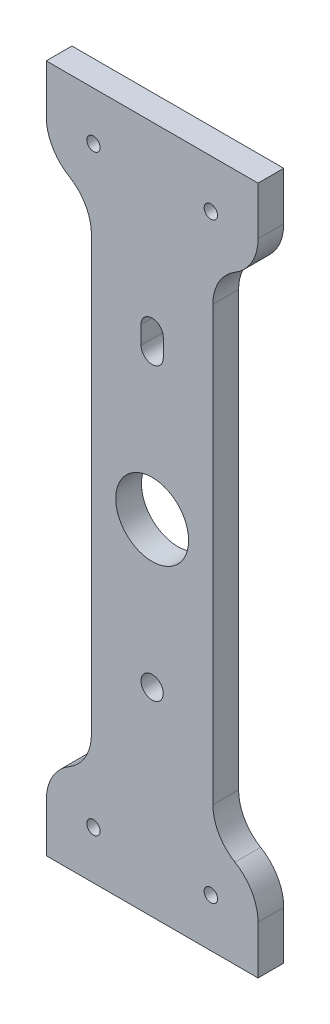
SolidWorks part; units mm, degrees
ref_plane "Front Plane" through (0, 0, 0) normal (0, 0, 1) x (1, 0, 0)
ref_plane "Top Plane" through (0, 0, 0) normal (0, 1, 0) x (1, 0, 0)
ref_plane "Right Plane" through (0, 0, 0) normal (1, 0, 0) x (0, 0, -1)
sketch "Sketch1" plane through (0, 0, 0) normal (0, 0, 1) x (1, 0, 0)
  line L0 (-15, -53.4948) -> (-15, 53.4948)
  line L1 (-26.15, 73.0938) -> (-26.15, 85)
  line L2 (-26.15, 85) -> (26.15, 85)
  line L3 (26.15, 85) -> (26.15, 73.0938)
  line L4 (15, 53.4948) -> (15, -53.4948)
  line L5 (-15, 0) -> (15, 0) construction
  line L6 (0, 85) -> (0, -85) construction
  line L7 (26.15, -85) -> (-26.15, -85)
  line L8 (-26.15, -85) -> (-26.15, -73.0938)
  line L9 (26.15, -73.0938) -> (26.15, -85)
  line L10 (0, 40.3109) -> (0, 35.8891) construction
  line L11 (2.75, 40.3109) -> (2.75, 35.8891)
  line L12 (-2.75, 40.3109) -> (-2.75, 35.8891)
  circle A0 centre (0, 0) radius 9
  arc A1 (-15, 53.4948) -> (-20.4527, 63.0794) centre (-26.15, 53.4948) ccw
  arc A2 (-20.4527, 63.0794) -> (-26.15, 73.0938) centre (-14.5, 73.0937) cw
  arc A3 (26.15, 73.0938) -> (20.4527, 63.0794) centre (14.5, 73.0938) cw
  arc A4 (20.4527, 63.0794) -> (15, 53.4948) centre (26.15, 53.4948) ccw
  arc A5 (-26.15, -73.0938) -> (-20.4527, -63.0794) centre (-14.5, -73.0937) cw
  arc A6 (-20.4527, -63.0794) -> (-15, -53.4948) centre (-26.15, -53.4948) ccw
  arc A7 (15, -53.4948) -> (20.4527, -63.0794) centre (26.15, -53.4948) ccw
  arc A8 (20.4527, -63.0794) -> (26.15, -73.0938) centre (14.5, -73.0938) cw
  circle A9 centre (14.5, 73.0938) radius 1.65
  circle A10 centre (-14.5, 73.0938) radius 1.65
  circle A11 centre (14.5, -73.0938) radius 1.65
  circle A12 centre (-14.5, -73.0938) radius 1.65
  circle A13 centre (0, 38.1) radius 4.9609 construction
  circle A14 centre (0, -38.1) radius 4.9609 construction
  circle A15 centre (0, -35.8891) radius 2.75
  arc A16 (2.75, 40.3109) -> (-2.75, 40.3109) centre (0, 40.3109) ccw
  arc A17 (-2.75, 35.8891) -> (2.75, 35.8891) centre (0, 35.8891) ccw
  point P16 (0, 85)
  point P25 (0, -85)
  point P49 (0, 38.1)
  point P54 (2.75, 35.9431)
  point P55 (2.75, 40.4001)
  dimension "D1" = 18
  dimension "D4" = 3.3
  dimension "D9" = 9.9219
  dimension "D10" = 5.5
  dimension "D2" = 170
  dimension "D3" = 30
  dimension "D5" = 146.1875
  dimension "D6" = 29
  dimension "D7" = 10
  dimension "D8" = 76.2
  dimension "D11" = 5.5
extrude "Boss-Extrude1" add sketch "Sketch1" along normal blind 6.35
equation "\"frame inside height\"= 170mm'`"
equation "\"hole spacing\"= 14.5mm"
equation "\"top hole to bottom hole\"= 146.18750000mm"
equation "\"D2@Sketch1\"=\"frame inside height\""
equation "\"D5@Sketch1\"=\"top hole to bottom hole\""
equation "\"D6@Sketch1\"=2*\"hole spacing\""
